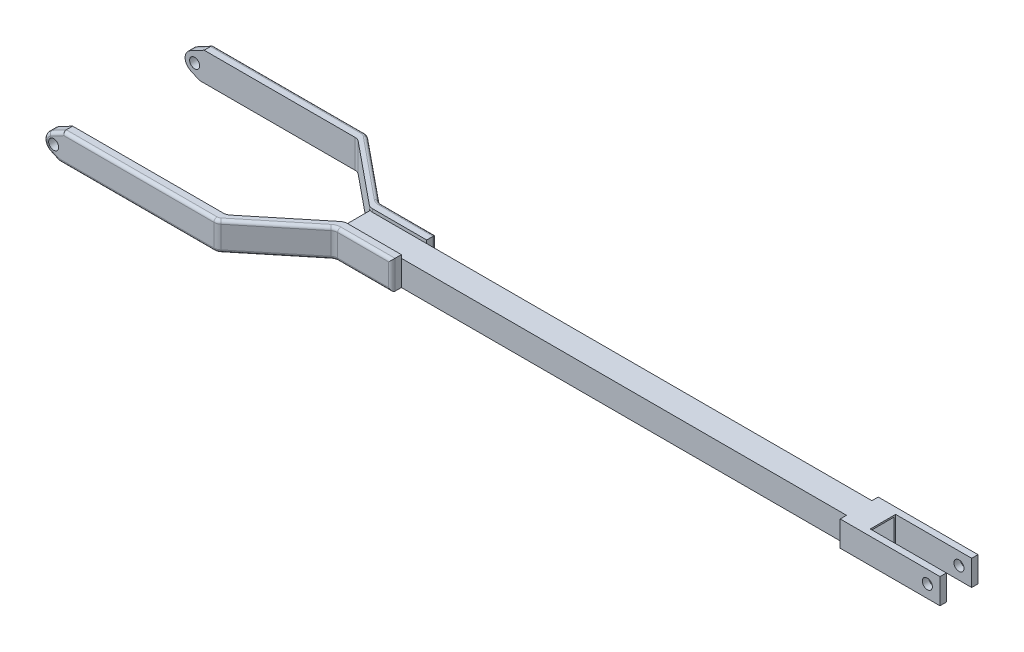
SolidWorks part; units mm, degrees
material "6061-T6 (SS)"
ref_plane "Front Plane" through (0, 0, 0) normal (0, 0, 1) x (1, 0, 0)
ref_plane "Top Plane" through (0, 0, 0) normal (0, 1, 0) x (1, 0, 0)
ref_plane "Right Plane" through (0, 0, 0) normal (1, 0, 0) x (0, 0, -1)
sketch "Sketch1" plane through (0, 0, 0) normal (0, 0, 1) x (1, 0, 0)
  line L1 (-40, -8) -> (-372, -8)
  line L2 (-40, -8) -> (-40, 8)
  line L3 (-40, 8) -> (-372, 8)
  line L4 (-372, -8) -> (-372, 8)
  circle A0 centre (0, 0) radius 3.175
  circle A1 centre (-516, 0) radius 3.175
  point P5 (-40, 0)
  dimension "D1" = 516
  dimension "D2" = 6.35
  dimension "D3" = 16
  dimension "D4" = 40
  dimension "D5" = 144
extrude "Boss-Extrude1" add sketch "Sketch1" against normal mid plane 16 contours L4 L1 L2 L3 region at (-206, 0, 0)
shell "Shell1" thickness 1 removed face at (-40, 0, 0) removed face at (-372, 0, 0)
sketch "Sketch2" plane through (-40, 0, 0) normal (1, 0, 0) x (0, 0, -1)
  line L1 (-8, 8) -> (-12, 8)
  line L2 (-8, 8) -> (-8, -8)
  line L3 (-8, -8) -> (-12, -8)
  line L4 (-8, 8) -> (-8, -8)
  line L5 (-8, -8) -> (8, -8)
  line L6 (8, -8) -> (8, 8)
  line L7 (8, 8) -> (-8, 8)
  line L8 (-8, 8) -> (-8, -8)
  line L9 (-8, -8) -> (8, -8)
  line L10 (8, -8) -> (8, 8)
  line L11 (8, 8) -> (-8, 8)
  line L12 (-12, 8) -> (-12, -8)
  line L13 (8, 8) -> (12, 8)
  line L14 (8, 8) -> (8, -8)
  line L15 (8, -8) -> (12, -8)
  line L16 (12, 8) -> (12, -8)
  line M13 (-8, 8) -> (-8, -8)
  line M15 (8, -8) -> (8, 8)
  dimension "D2" = 4
  dimension "D1" = 0
extrude "Boss-Extrude2" add sketch "Sketch2" along normal blind 48 and the other way blind 15 contours L1 L12 L3 M13 | L16 L13 L15 M15 region at (-40, 0, 10) region at (-40, 0, -10)
sketch "Sketch3" plane through (0, 8, 0) normal (0, 1, 0) x (1, 0, 0)
  line L0 (-55, -8) -> (-372, -8) construction
  line L1 (-336, -8) -> (-372, -8)
  line L2 (-336, -8) -> (-336, -14)
  line L3 (-336, -14) -> (-372, -14)
  line L5 (-372, 8) -> (-372, -8) construction
  line L6 (-372, -8) -> (-413, -41.5)
  line L7 (-413, -41.5) -> (-522, -41.5)
  line L8 (-372, -14) -> (-413, -47.5)
  line L9 (-413, -47.5) -> (-522, -47.5)
  line L10 (-40, 0) -> (-372, 0) construction
  line L11 (-522, -41.5) -> (-522, -47.5)
  line L12 (-519.175, 0) -> (-512.825, 0) construction
  line L13 (-519.175, 0) -> (-512.825, 0)
  point P14 (-516, 0)
  line M10 (-372, -8) -> (-55, -8)
  dimension "D1" = 36
  dimension "D2" = 6
  dimension "D3" = 6
  dimension "D4" = 47.5
  dimension "D5" = 6
  dimension "D6" = 41
extrude "Boss-Extrude3" add sketch "Sketch3" against normal up to surface (16 mm away) and the other way blind 2 contours L7 L11 L9 L8 L3 L2 L6 M10 region at (-337.9015, 8, 11) up to face at (-84.3333, -8, 0)
sketch "Sketch4" plane through (0, 0, 47.5) normal (0, 0, 1) x (1, 0, 0)
  line L0 (-510, 10) -> (-518.8235, 5.2941)
  line L1 (-413, 10) -> (-522, 10) construction
  line L2 (-513, -8) -> (-518.5202, -5.4451)
  line L4 (-522, -8) -> (-522, 10) construction
  line L5 (-522, 10) -> (-522, -8) construction
  line L6 (-510, 10) -> (-542.3148, 28.0704)
  line L7 (-542.3148, 28.0704) -> (-540.2777, -26.3694)
  line L8 (-540.2777, -26.3694) -> (-513, -8)
  line L9 (-522, -8) -> (-413, -8) construction
  arc A0 (-518.8235, 5.2941) -> (-518.5202, -5.4451) centre (-516, 0) ccw
  dimension "D3" = 12
  dimension "D1" = 12
  dimension "D2" = 9
extrude "Cut-Extrude1" cut sketch "Sketch4" against normal blind 40 contours L7 L8 L2 A0 L0 L6
fillet "Fillet1" radius 5 4 edges at (-372, 9, 8) (-413, 1, 41.5) (-372, 1, 14) (-413, 1, 47.5)
fillet "Fillet2" radius 2 14 edges at (-371.8964, -8, 14.2905) (-413.1036, -8, 47.2095) (-353.1085, 10, 14) (-371.8964, 10, 14.2905) (-392.5, 10, 30.75) (-413.1036, 10, 47.2095) (-515.7601, -6.7225, 47.5) (-521.9976, -0.1694, 47.5) (-336, 1, 14) (-462.3915, 10, 47.5) (-514.4118, 7.6471, 47.5) (-463.8915, -8, 47.5) (-353.1085, -8, 14) (-392.5, -8, 30.75)
mirror "Mirror1" about plane through (0, 0, 0) normal (0, 0, 1) of "Fillet2", "Fillet1", "Cut-Extrude1", "Boss-Extrude3"
extrude "Cut-Extrude2" cut sketch "Sketch1<3>" against normal through all both and the other way through all contours A1 | A0 region at (0, 0, 0) region at (-516, 0, 0)
sketch "Sketch1<3>" plane through (0, 0, 0) normal (0, 0, 1) x (1, 0, 0) same geometry as "Sketch1"
